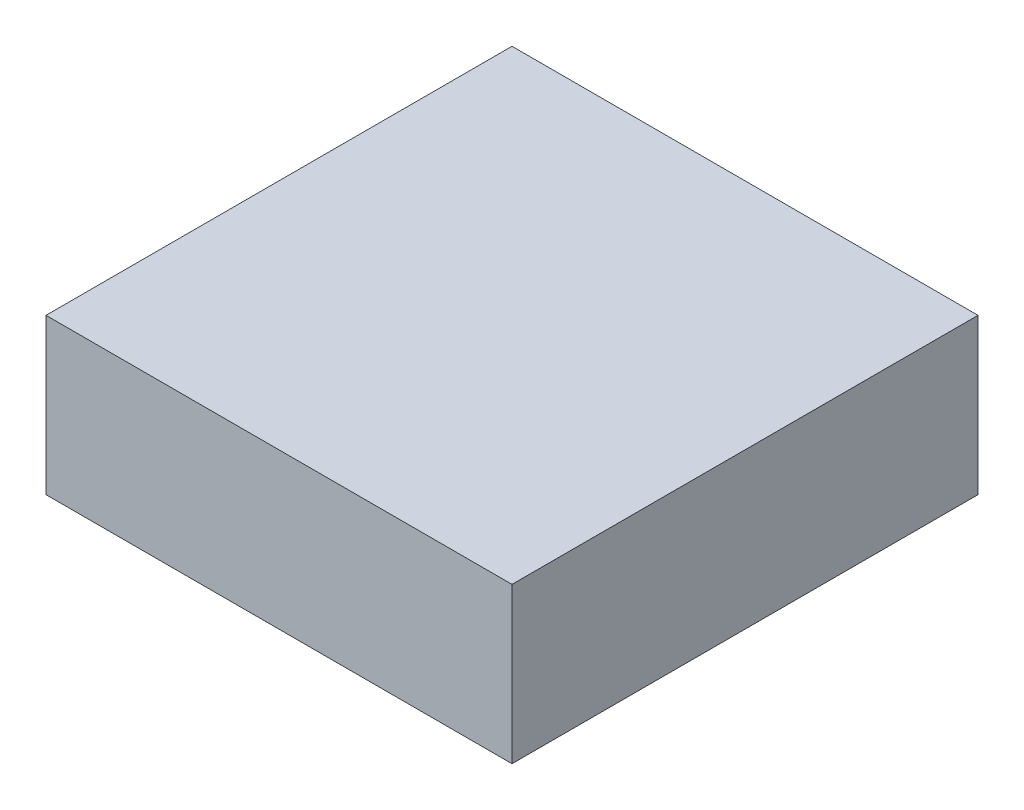
SolidWorks part; units mm, degrees
ref_plane "Front Plane" through (0, 0, 0) normal (0, 0, 1) x (1, 0, 0)
ref_plane "Top Plane" through (0, 0, 0) normal (0, 1, 0) x (1, 0, 0)
ref_plane "Right Plane" through (0, 0, 0) normal (1, 0, 0) x (0, 0, -1)
sketch "Sketch1" plane through (0, 0, 0) normal (0, 1, 0) x (1, 0, 0)
  line L1 (-11.5, -3.5) -> (11.5, -3.5)
  line L2 (-11.5, -3.5) -> (-11.5, 3.5)
  line L3 (-11.5, 3.5) -> (11.5, 3.5)
  line L4 (11.5, -3.5) -> (11.5, 3.5)
  line L5 (-11.5, -3.5) -> (11.5, 3.5) construction
  line L6 (-11.5, 3.5) -> (11.5, -3.5) construction
  line L7 (-15, -15) -> (15, -15)
  line L8 (-15, -15) -> (-15, 15)
  line L9 (-15, 15) -> (15, 15)
  line L10 (15, -15) -> (15, 15)
  line L11 (-15, -15) -> (15, 15) construction
  line L12 (-15, 15) -> (15, -15) construction
  point P0 (0, 0)
  point P6 (0, 0)
  dimension "D1" = 23
  dimension "D2" = 7
  dimension "D3" = 30
extrude "Boss-Extrude1" add sketch "Sketch1" along normal blind 10
extrude "Boss-Extrude2" add sketch "Sketch1<2>" along normal blind 3 from offset 7 contours L1 L4 L3 L2 region at (0, 0, 0)
sketch "Sketch1<2>" plane through (0, 0, 0) normal (0, 1, 0) x (1, 0, 0) same geometry as "Sketch1"
